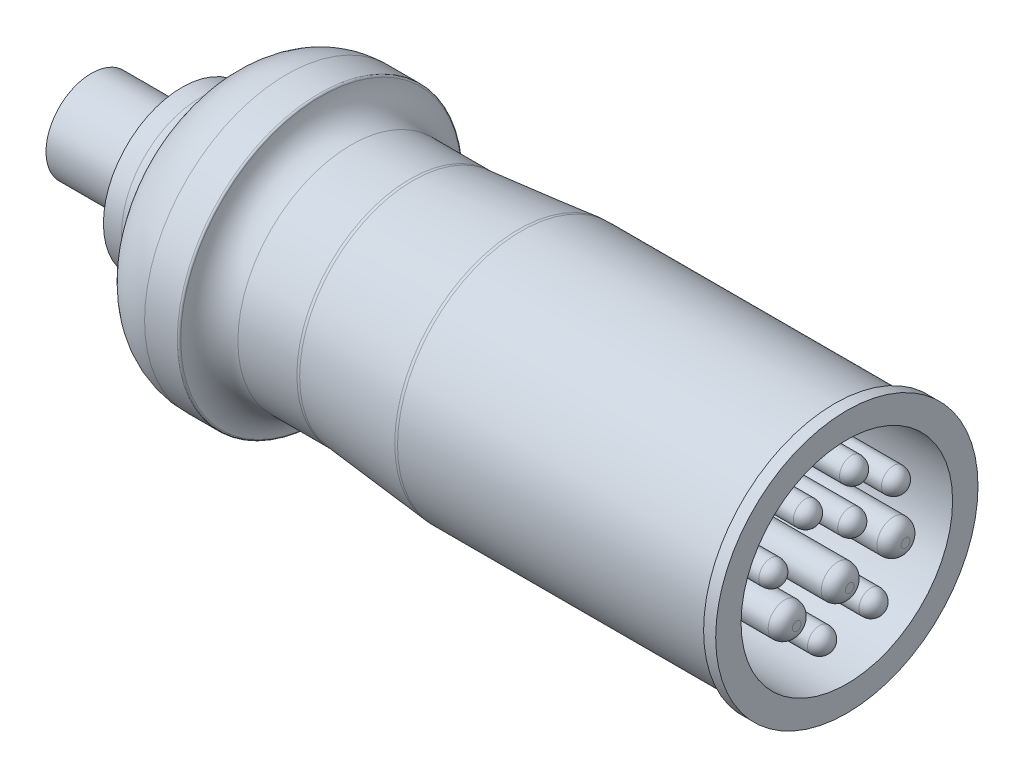
SolidWorks part; units mm, degrees
ref_plane "Front Plane" through (0, 0, 0) normal (0, 0, 1) x (1, 0, 0)
ref_plane "Top Plane" through (0, 0, 0) normal (0, 1, 0) x (1, 0, 0)
ref_plane "Right Plane" through (0, 0, 0) normal (1, 0, 0) x (0, 0, -1)
sketch "Sketch3" plane through (0, 0, 0) normal (0, 0, 1) x (1, 0, 0)
  line L0 (0, 0) -> (0, -50000) construction
  line L1 (0, 0) -> (50000, 0) construction
  line L2 (65, 0) -> (65, 20.5)
  line L3 (65, 17.5) -> (11.0609, 17.5) construction
  line L4 (11.0609, 17.5) -> (-6.8538, 15.75) construction
  line L5 (-6.8538, 15.75) -> (-25, 15.75) construction
  line L6 (-25, 15.75) -> (-25, 20.5) construction
  line L7 (-42, 0) -> (-42, 53.8042) construction
  line L8 (-25, 20.5) -> (-27.6909, 20.5) construction
  line L9 (-42, 10) -> (-43.4514, 10) construction
  line L10 (-42, 13) -> (-42, 0) construction
  line L11 (-42, 0) -> (65, 0)
  line L12 (65, 20.5) -> (10.9147, 20.5)
  line L13 (10.9147, 20.5) -> (-7, 18.75)
  line L14 (-7, 18.75) -> (-22, 18.75)
  line L15 (-22, 18.75) -> (-22, 23.5)
  line L16 (-22, 23.5) -> (-27.6909, 23.5)
  line L17 (-42, 13) -> (-45, 13)
  line L18 (-45, 13) -> (-45, 0)
  line L19 (-45, 0) -> (-42, 0)
  arc A0 (-42, 10) -> (-35.3224, 14.9) centre (-42, 17) ccw construction
  arc A1 (-35.3224, 14.9) -> (-27.6909, 20.5) centre (-27.6909, 12.5) cw construction
  arc A2 (-38.1842, 15.8) -> (-27.6909, 23.5) centre (-27.6909, 12.5) cw
  arc A3 (-42, 13) -> (-38.1842, 15.8) centre (-42, 17) ccw
  dimension "D8" = 20
  dimension "D9" = 7
  dimension "D10" = 8
  dimension "D1" = 17.5
  dimension "D2" = 23
  dimension "D3" = 18
  dimension "D4" = 15.75
  dimension "D5" = 41
  dimension "D6" = 110
  dimension "D7" = 3
  dimension "D11" = 3
  dimension "D12" = 45
  dimension "D13" = 15
revolve "Revolve1" add sketch "Sketch3" angle 360 about L1
fillet "Fillet1" radius 5 1 edges at (-22, 0, 18.75)
fillet "Fillet2" radius 0.3 1 edges at (-22, 0, 23.5)
fillet "Fillet3" radius 5 2 edges at (10.9147, 0, 20.5) (-7, 0, 18.75)
sketch "Sketch4" plane through (65, 0, 0) normal (1, 0, 0) x (0, 0, -1)
  circle A2 centre (0, 0) radius 17.5
  circle A3 centre (0, 0) radius 17.5
  dimension "D1" = 3
extrude "Cut-Extrude1" cut sketch "Sketch4" against normal blind 35
sketch "Sketch5" plane through (30, 0, 0) normal (1, 0, 0) x (0, 0, -1)
  line L0 (0, 0) -> (0, -50000) construction
  line L1 (0, 0) -> (50000, 0) construction
  circle A0 centre (2.4852, 3.5673) radius 2.0006
  circle A1 centre (2.7845, 10.8694) radius 2.0006
  circle A2 centre (-4.8439, 8.4442) radius 2.0006
  circle A3 centre (-10.5763, 2.8441) radius 2.0006
  circle A4 centre (9.7074, 5.9308) radius 2.0006
  circle A5 centre (-2.5069, -10.8694) radius 2.0006
  circle A6 centre (6.0034, -9.7229) radius 2.0006
  circle A7 centre (9.7074, -2.1386) radius 2.7332
  circle A8 centre (0.4915, -3.9906) radius 2.7332
  circle A9 centre (-8.2833, -5.0489) radius 2.7332
extrude "Boss-Extrude1" add sketch "Sketch5" along normal up to surface (35 mm away) up to face at (65, 0, -17.5)
fillet "Fillet4" radius 2 10 edges at (65, -10.8694, 4.5075) (65, -9.7229, -4.0028) (65, -2.1386, -6.9742) (65, -3.9906, 2.2416) (65, -5.0489, 11.0165) (65, 2.8441, 12.5769) (65, 3.5673, -0.4846) (65, 5.9308, -7.7068) (65, 10.8694, -0.7839) (65, 8.4442, 6.8446)
sketch "Sketch6" plane through (65, 0, 0) normal (1, 0, 0) x (0, 0, -1)
  circle A0 centre (0, 0) radius 20.5 construction
  circle A1 centre (0, 0) radius 20.5
  circle A2 centre (0, 0) radius 21.7
  dimension "D1" = 1.2
extrude "Boss-Extrude2" add sketch "Sketch6" against normal blind 2
sketch "Sketch7" plane through (-45, 0, 0) normal (-1, 0, 0) x (0, 0, 1)
  circle A0 centre (0, 0) radius 7.5
  dimension "D1" = 15
extrude "Extrude-Thin1" add sketch "Sketch7" along normal blind 15 thin thin type one direction reverse wall 0.5
